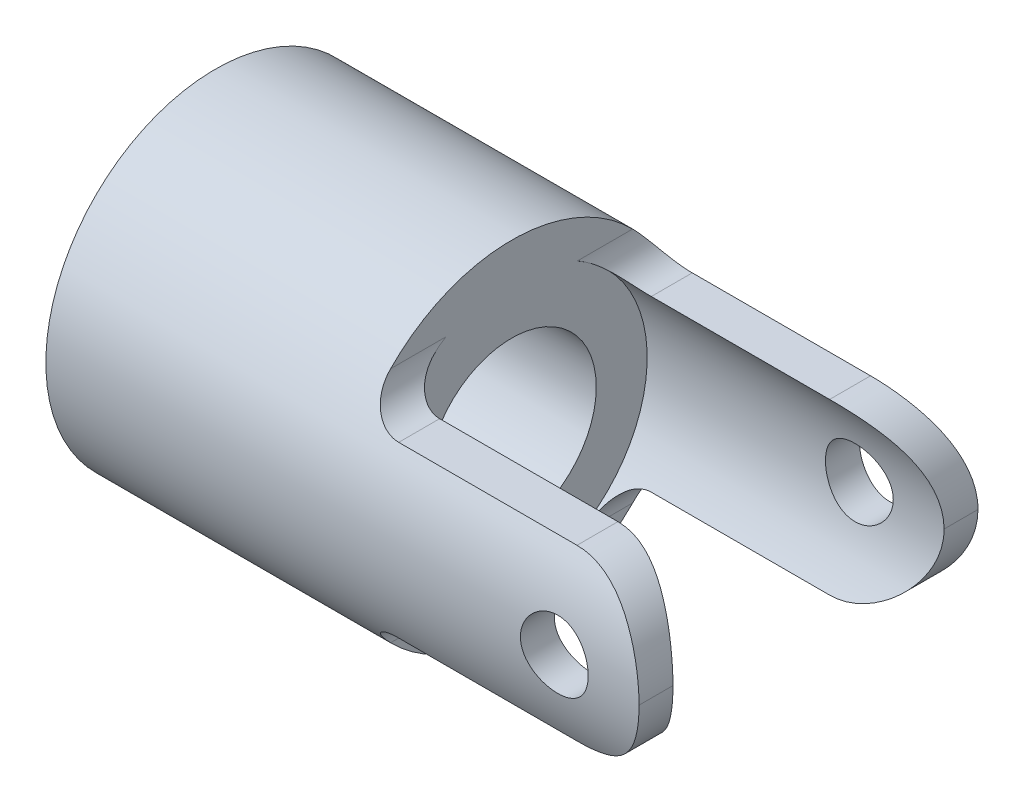
SolidWorks part; units mm, degrees
ref_plane "Front Plane" through (0, 0, 0) normal (0, 0, 1) x (1, 0, 0)
ref_plane "Top Plane" through (0, 0, 0) normal (0, 1, 0) x (1, 0, 0)
ref_plane "Right Plane" through (0, 0, 0) normal (1, 0, 0) x (0, 0, -1)
ref_plane "Flange BottomPlane" through (-19.05, 0, 0) normal (1, 0, 0) x (0, 0, -1)
sketch "Sketch1" plane through (-19.05, 0, 0) normal (1, 0, 0) x (0, 0, -1)
  circle A0 centre (0, 0) radius 6.35
  dimension "B" = 12.7
extrude "Flange Bottom" add sketch "Sketch1" along normal blind 7.9248
sketch "Sketch2" plane through (-11.1252, 0, 0) normal (1, 0, 0) x (0, 0, -1)
  circle A0 centre (0, 0) radius 6.35
  dimension "D1" = 12.7
extrude "Flangmidbody" add sketch "Sketch2" along normal blind 3.175
sketch "Sketch3" plane through (-7.9502, 0, 0) normal (1, 0, 0) x (0, 0, -1)
  line L0 (-5.4993, 3.175) -> (-3.9656, 3.175)
  line L1 (-7.5926, 0) -> (7.3734, 0) construction
  line L2 (6.985, 0) -> (-6.985, 0) construction
  line L3 (-5.4993, -3.175) -> (-3.9656, -3.175)
  line L4 (3.9656, 3.175) -> (5.4993, 3.175)
  line L5 (3.9656, -3.175) -> (5.4993, -3.175)
  circle A0 centre (0, 0) radius 6.35 construction
  arc A1 (-5.4993, 3.175) -> (-5.4993, -3.175) centre (0, 0) ccw
  arc A2 (-3.9656, 3.175) -> (-3.9656, -3.175) centre (0, 0) ccw
  arc A3 (3.9656, -3.175) -> (3.9656, 3.175) centre (0, 0) ccw
  arc A4 (5.4993, -3.175) -> (5.4993, 3.175) centre (0, 0) ccw
  dimension "D1" = 10.16
  dimension "D2" = 6.35
extrude "Flangelegs" add sketch "Sketch3" along normal offset from surface (11.1252 mm away) 3.175 up to plane "Right Plane" offset beyond the face yes
fillet "Fillet1" radius 3.175 4 edges at (3.175, -3.175, -4.7324) (3.175, 3.175, -4.7324) (3.175, -3.175, 4.7324) (3.175, 3.175, 4.7324)
sketch "Sketch4" plane through (0, 0, 0) normal (0, 0, 1) x (1, 0, 0)
  circle A0 centre (0, 0) radius 1.27
  dimension "D1" = 2.54
extrude "Lockingshafthole" cut sketch "Sketch4" against normal through all and the other way through all
fillet "Fillet3" radius 1.27 4 edges at (-7.9502, 3.175, -4.7324) (-7.9502, -3.175, -4.7324)
sketch "Sketch5" plane through (-19.05, 0, 0) normal (-1, 0, 0) x (0, 0, 1)
  circle A0 centre (0, 0) radius 3.1725
  dimension "A" = 6.3449
extrude "CenterShaftHole" cut sketch "Sketch5" against normal through all
ref_plane "LockingScrewPlane" through (0, -6.35, 0) normal (0, 1, 0) x (-1, 0, 0)
sketch "Sketch11" plane through (0, 0, 0) normal (0, 1, 0) x (1, 0, 0)
  circle A0 centre (-15.0876, 0) radius 0.8736
  point P2 (0, 0)
  dimension "D1" = 1.7471
extrude "Set Screw" cut sketch "Sketch11" against normal through all
ref_plane "SubHolePlane" through (0, 0, -6.35) normal (0, 0, 1) x (1, 0, 0)
ref_axis "Axis1" through (0, 0, 6.985) along (0, 0, -1)
sketch "Sketch12" plane through (0, 0, -6.35) normal (0, 0, 1) x (1, 0, 0)
  line L0 (-15.0876, 0) -> (-15.0876, -1.3226) construction
  line L2 (-15.9612, -3.1725) -> (-15.9612, -6.35) construction
  line L3 (-14.214, -6.35) -> (-14.214, -3.1725) construction
  circle A0 centre (-15.0876, 0) radius 0.8736
extrude "Sub Drill" cut sketch "Sketch12" along normal blind 1.27
equation "\"D1@Flangelegs\" = \"D2@Sketch3\"*.5"
equation "\"D1@Fillet1\" = \"D1@Flangelegs\""
equation "\"D1@LockingScrewPlane\" = \"B@Sketch1\" * .5"
equation "\"D1@SubHolePlane\" = \"D1@LockingScrewPlane\""
